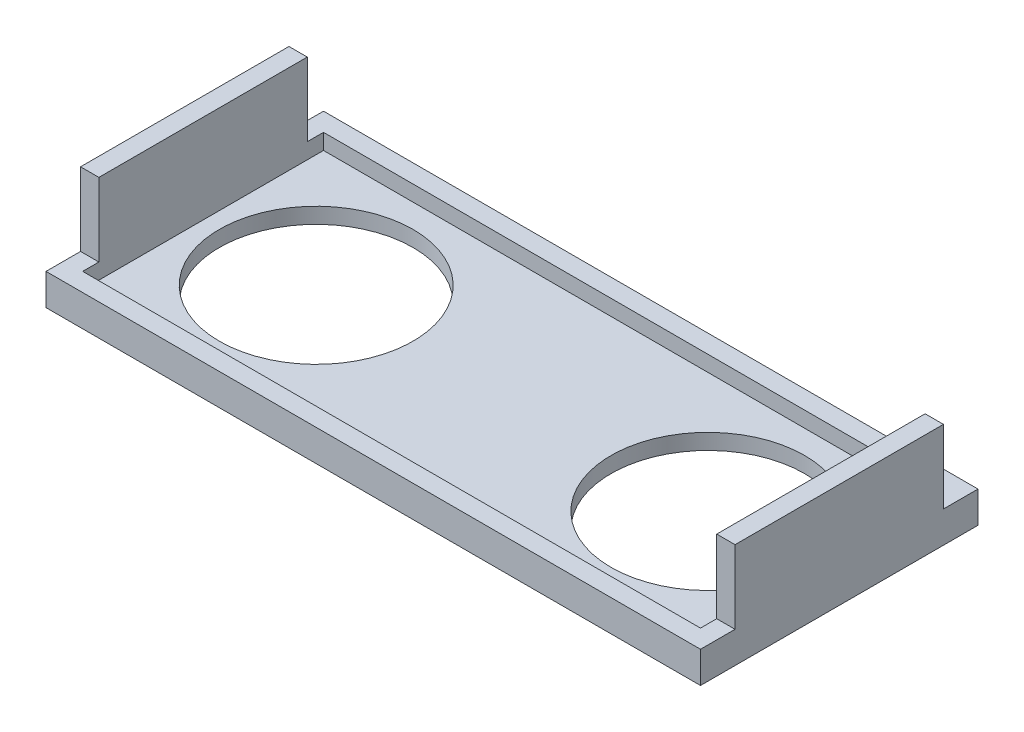
SolidWorks part; units mm, degrees
ref_plane "Front Plane" through (0, 0, 0) normal (0, 0, 1) x (1, 0, 0)
ref_plane "Top Plane" through (0, 0, 0) normal (0, 1, 0) x (1, 0, 0)
ref_plane "Right Plane" through (0, 0, 0) normal (1, 0, 0) x (0, 0, -1)
sketch "Croquis1" plane through (0, 0, 0) normal (0, 1, 0) x (1, 0, 0)
  line L1 (-31.25, 13.25) -> (31.25, 13.25)
  line L2 (-31.25, 13.25) -> (-31.25, -13.25)
  line L3 (-31.25, -13.25) -> (31.25, -13.25)
  line L4 (31.25, 13.25) -> (31.25, -13.25)
  line L5 (-31.25, 13.25) -> (31.25, -13.25) construction
  line L6 (-31.25, -13.25) -> (31.25, 13.25) construction
  point P0 (0, 0)
  dimension "D1" = 62.5
  dimension "D2" = 26.5
extrude "Saliente-Extruir1" add sketch "Croquis1" along normal mid plane 3
sketch "Croquis4" plane through (0, 0, 0) normal (0, 1, 0) x (1, 0, 0)
  line L1 (-29.5, 11.5) -> (29.5, 11.5)
  line L2 (-29.5, 11.5) -> (-29.5, -11.5)
  line L3 (-29.5, -11.5) -> (29.5, -11.5)
  line L4 (29.5, 11.5) -> (29.5, -11.5)
  line L5 (-29.5, 11.5) -> (29.5, -11.5) construction
  line L6 (-29.5, -11.5) -> (29.5, 11.5) construction
  point P0 (0, 0)
  dimension "D1" = 59
  dimension "D2" = 23
extrude "Cortar-Extruir1" cut sketch "Croquis4" against normal blind 1.5 from surface starting at face at (0, 1.5, 0)
sketch "Croquis5" plane through (0, 0, 0) normal (0, 1, 0) x (1, 0, 0)
  line L1 (-27.95, 0) -> (-31.25, 0) construction
  line L2 (-31.25, 13.25) -> (-31.25, -13.25) construction
  line L3 (0, 8.4298) -> (0, -7.9321) construction
  line L4 (18.7, 9.25) -> (18.7, 13.25) construction
  line L5 (31.25, 13.25) -> (-31.25, 13.25) construction
  line L6 (-18.7, 9.25) -> (-18.7, 13.25) construction
  circle A0 centre (-18.7, 0) radius 9.25
  circle A1 centre (18.7, 0) radius 9.25
  dimension "D1" = 3.3
  dimension "D2" = 18.5
extrude "Cortar-Extruir2" cut sketch "Croquis5" against normal blind 1.5
sketch "Croquis6" plane through (0, 0, 0) normal (1, 0, 0) x (0, 0, -1)
  line L0 (0, 1.5) -> (0, -1.5) construction
  line L1 (-9.95, -1.5) -> (-9.95, 8.5)
  line L2 (-9.95, 8.5) -> (9.95, 8.5)
  line L3 (-13.25, 1.5) -> (13.25, 1.5) construction
  line L4 (-13.25, -1.5) -> (13.25, -1.5) construction
  line L5 (9.95, 8.5) -> (9.95, -1.5)
  line L6 (9.95, -1.5) -> (-9.95, -1.5)
  dimension "D1" = 9.95
  dimension "D2" = 9.95
  dimension "D3" = 10
extrude "Saliente-Extruir2" add sketch "Croquis6" against normal blind 1.75 from surface starting at face at (31.25, 0, 0)
extrude "Saliente-Extruir3" add sketch "Croquis6<3>" along normal blind 1.75 from surface starting at face at (-31.25, 0, 0)
sketch "Croquis6<3>" plane through (0, 0, 0) normal (1, 0, 0) x (0, 0, -1) same geometry as "Croquis6"
